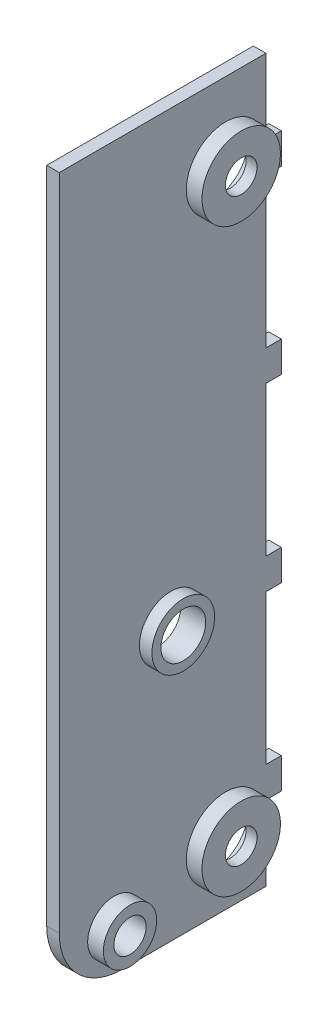
SolidWorks part; units mm, degrees
ref_plane "Front Plane" through (0, 0, 0) normal (0, 0, 1) x (1, 0, 0)
ref_plane "Top Plane" through (0, 0, 0) normal (0, 1, 0) x (1, 0, 0)
ref_plane "Right Plane" through (0, 0, 0) normal (1, 0, 0) x (0, 0, -1)
sketch "Sketch1" plane through (0, 0, 0) normal (0, 0, 1) x (1, 0, 0)
  line L1 (-100, -115) -> (100, -115)
  line L2 (-100, -115) -> (-100, 115)
  line L3 (-100, 115) -> (100, 115)
  line L4 (100, -115) -> (100, 115)
  line L5 (-100, -115) -> (100, 115) construction
  line L6 (-100, 115) -> (100, -115) construction
  point P0 (0, 0)
  dimension "D1" = 230
  dimension "D2" = 200
extrude "Boss-Extrude1" add sketch "Sketch1" along normal blind 70
sketch "Sketch2" plane through (0, 0, 70) normal (0, 0, 1) x (1, 0, 0)
  line L0 (100, 115) -> (-100, 115) construction
  line L1 (-96, -111) -> (96, -111)
  line L2 (-96, -111) -> (-96, 111)
  line L3 (-96, 111) -> (96, 111)
  line L4 (96, -111) -> (96, 111)
  line L5 (-96, -111) -> (96, 111) construction
  line L6 (-96, 111) -> (96, -111) construction
  line L7 (-100, 115) -> (-100, -115) construction
  point P0 (0, 0)
  dimension "D1" = 4
  dimension "D2" = 4
extrude "Cut-Extrude1" cut sketch "Sketch2" against normal blind 66
sketch "Sketch4" plane through (0, -115, 0) normal (0, -1, 0) x (1, 0, 0)
  line L0 (-100, 70) -> (-100, 0) construction
  line L1 (-98, 45) -> (98, 45)
  line L2 (-98, 45) -> (-98, 70)
  line L3 (-98, 70) -> (98, 70)
  line L4 (98, 45) -> (98, 70)
  line L5 (100, 70) -> (100, 0) construction
  line L6 (-100, 70) -> (100, 70) construction
  dimension "D1" = 2
  dimension "D2" = 2
  dimension "D3" = 0
  dimension "D4" = 25
extrude "Cut-Extrude3" cut sketch "Sketch4" against normal blind 10
sketch "Sketch10" plane through (0, 0, 4) normal (0, 0, 1) x (1, 0, 0)
  line L0 (-96, 111) -> (-96, -111) construction
  line L1 (-96, -111) -> (96, -111) construction
  circle A0 centre (0, -11) radius 5
  dimension "D1" = 10
  dimension "D2" = 96
  dimension "D3" = 100
extrude "Cut-Extrude8" cut sketch "Sketch10" against normal through all
sketch "Sketch11" plane through (0, 0, 70) normal (0, 0, 1) x (1, 0, 0)
  line L0 (-98, -105) -> (-98, -115) construction
  line L1 (-98, -105) -> (-100, -105)
  line L2 (-98, -105) -> (-98, -115)
  line L3 (-98, -115) -> (-100, -115)
  line L4 (-100, -105) -> (-100, -115)
  dimension "D1" = 10
extrude "Boss-Extrude2" add sketch "Sketch11" along normal blind 20
sketch "Sketch12" plane through (0, 0, 90) normal (0, 0, 1) x (1, 0, 0)
  line L0 (-100, -105) -> (-100, -115) construction
  line L1 (-100, -107.5) -> (-98, -107.5)
  line L2 (-100, -107.5) -> (-100, -112.5)
  line L3 (-100, -112.5) -> (-98, -112.5)
  line L4 (-98, -107.5) -> (-98, -112.5)
  line L5 (-98, -115) -> (-98, -105) construction
  line L6 (-98, -105) -> (-100, -105) construction
  dimension "D1" = 2.5
  dimension "D2" = 5
extrude "Cut-Extrude9" cut sketch "Sketch12" against normal blind 20
fillet "Fillet1" radius 2.5 2 edges at (-99, -112.5, 70) (-99, -107.5, 70)
sketch "Sketch13" plane through (0, 0, 70) normal (0, 0, 1) x (1, 0, 0)
  line L0 (98, -115) -> (100, -115) construction
  line L1 (98, -105) -> (100, -105)
  line L2 (98, -105) -> (98, -115)
  line L3 (98, -115) -> (100, -115)
  line L4 (100, -105) -> (100, -115)
  dimension "D1" = 0
  dimension "D2" = 2
extrude "Boss-Extrude3" add sketch "Sketch13" along normal blind 20
sketch "Sketch14" plane through (0, 0, 90) normal (0, 0, 1) x (1, 0, 0)
  line L0 (98, -105) -> (98, -115) construction
  line L1 (98, -107.5) -> (100, -107.5)
  line L2 (98, -107.5) -> (98, -112.5)
  line L3 (98, -112.5) -> (100, -112.5)
  line L4 (100, -107.5) -> (100, -112.5)
  line L5 (100, -115) -> (100, -105) construction
  line L6 (98, -105) -> (96, -105) construction
  dimension "D1" = 2.5
  dimension "D2" = 5
extrude "Cut-Extrude10" cut sketch "Sketch14" against normal blind 20
fillet "Fillet2" radius 2.5 2 edges at (99, -112.5, 70) (99, -107.5, 70)
sketch "Sketch15" plane through (0, 115, 0) normal (0, 1, 0) x (1, 0, 0)
  line L0 (100, -70) -> (-100, -70) construction
  line L1 (96, -70) -> (-96, -70)
  line L2 (96, -70) -> (96, -4)
  line L3 (96, -4) -> (-96, -4)
  line L4 (-96, -70) -> (-96, -4)
  line L5 (-100, -70) -> (-100, 0) construction
  line L6 (100, -70) -> (100, 0) construction
  line L7 (100, 0) -> (-100, 0) construction
  dimension "D1" = 4
  dimension "D2" = 4
  dimension "D3" = 4
extrude "Cut-Extrude11" cut sketch "Sketch15" against normal through all
sketch "Sketch16" plane through (-98, 0, 0) normal (1, 0, 0) x (0, 0, -1)
  line L0 (-90, -107.5) -> (-72.5, -107.5)
  line L1 (-72.5, -112.5) -> (-90, -112.5)
  line L2 (-90, -112.5) -> (-90, -115)
  line L3 (-90, -115) -> (-45, -115)
  line L4 (-45, -115) -> (-45, -105)
  line L5 (-45, -105) -> (-90, -105)
  line L6 (-90, -105) -> (-90, -107.5)
  arc A0 (-72.5, -107.5) -> (-72.5, -112.5) centre (-72.5, -110) cw
extrude "Boss-Extrude4" add sketch "Sketch16" along normal blind 2
sketch "Sketch18" plane through (100, 0, 0) normal (1, 0, 0) x (0, 0, -1)
  line L0 (-70, -105) -> (-70, 115) construction
  line L1 (-70, 115) -> (0, 115) construction
  circle A0 centre (-34.45, -28.4) radius 7.15
  dimension "D2" = 14.3
  dimension "D1" = 35.55
  dimension "D3" = 143.4
extrude "Cut-Extrude12" cut sketch "Sketch18" against normal through all
sketch "Sketch19" plane through (100, 0, 0) normal (1, 0, 0) x (0, 0, -1)
  line L0 (-90, -115) -> (0, -115) construction
  line L1 (0, -115) -> (0, 115) construction
  circle A0 centre (-17, -95) radius 5.05
  dimension "D1" = 10.1
  dimension "D2" = 20
  dimension "D3" = 17
extrude "Cut-Extrude13" cut sketch "Sketch19" against normal through all
sketch "Sketch20" plane through (100, 0, 0) normal (1, 0, 0) x (0, 0, -1)
  line L0 (-70, 115) -> (0, 115) construction
  line L1 (0, -115) -> (0, 115) construction
  circle A0 centre (-17, 90) radius 5.05
  dimension "D1" = 10.1
  dimension "D2" = 25
  dimension "D3" = 17
extrude "Cut-Extrude14" cut sketch "Sketch20" against normal through all
sketch "Sketch17" plane through (98, 0, 0) normal (-1, 0, 0) x (0, 0, 1)
  line L0 (90, -107.5) -> (72.5, -107.5)
  line L1 (72.5, -112.5) -> (90, -112.5)
  line L2 (90, -112.5) -> (90, -115)
  line L3 (90, -115) -> (45, -115)
  line L4 (45, -115) -> (45, -105)
  line L5 (45, -105) -> (90, -105)
  line L6 (90, -105) -> (90, -107.5)
  arc A0 (72.5, -107.5) -> (72.5, -112.5) centre (72.5, -110) ccw
extrude "Boss-Extrude5" add sketch "Sketch17" along normal blind 2
sketch "Sketch21" plane through (100, 0, 0) normal (1, 0, 0) x (0, 0, -1)
  line L1 (-90, -115) -> (-70, -115)
  line L2 (-90, -115) -> (-90, -105)
  line L3 (-90, -105) -> (-70, -105)
  line L4 (-70, -115) -> (-70, -105)
extrude "Cut-Extrude15" cut sketch "Sketch21" against normal through all
sketch "Sketch22" plane through (0, 0, 4) normal (0, 0, 1) x (1, 0, 0)
  line L0 (96, 115) -> (-96, 115) construction
  line L1 (46, 75) -> (-46, 75)
  line L2 (46, 75) -> (46, 115)
  line L3 (46, 115) -> (-46, 115)
  line L4 (-46, 75) -> (-46, 115)
  line L5 (96, -115) -> (96, 115) construction
  line L6 (-96, 115) -> (-96, -115) construction
  dimension "D1" = 50
  dimension "D2" = 50
  dimension "D3" = 40
extrude "Cut-Extrude16" cut sketch "Sketch22" against normal blind 10
sketch "Sketch24" plane through (100, 0, 0) normal (1, 0, 0) x (0, 0, -1)
  line L0 (-70, -115) -> (-70, 115) construction
  line L1 (-70, -115) -> (0, -115) construction
  circle A0 centre (-52.45, -102) radius 5.15
  dimension "D1" = 10.3
  dimension "D2" = 17.55
  dimension "D3" = 13
extrude "Cut-Extrude18" cut sketch "Sketch24" against normal through all
fillet "Fillet3" radius 20 1 edges at (98, -115, 70)
fillet "Fillet4" radius 20 1 edges at (-98, -115, 70)
sketch "Sketch25" plane through (0, 115, 0) normal (0, 1, 0) x (1, 0, 0)
  line L0 (-100, -70) -> (-100, 0) construction
  line L1 (100, 0) -> (-100, 0)
  line L2 (100, 0) -> (100, -4.1191)
  line L3 (100, -4.1191) -> (-100, -4.1191)
  line L4 (-100, 0) -> (-100, -4.1191)
extrude "Cut-Extrude19" cut sketch "Sketch25" against normal through all
sketch "Sketch26" plane through (0, 115, 0) normal (0, 1, 0) x (1, 0, 0)
  line L1 (-96, -70) -> (-100, -70)
  line L2 (-96, -70) -> (-96, -4.1191)
  line L3 (-96, -4.1191) -> (-100, -4.1191)
  line L4 (-100, -70) -> (-100, -4.1191)
extrude "Cut-Extrude20" cut sketch "Sketch26" against normal through all
sketch "Sketch27" plane through (0, 0, 4.1191) normal (0, 0, -1) x (-1, 0, 0)
  line L0 (-100, -115) -> (-100, 115) construction
  line L1 (-100, -91.15) -> (-96, -91.15)
  line L2 (-100, -91.15) -> (-100, -81.35)
  line L3 (-100, -81.35) -> (-96, -81.35)
  line L4 (-96, -91.15) -> (-96, -81.35)
  line L5 (-96, 115) -> (-96, -115) construction
  line L6 (-96, -115) -> (-100, -115) construction
  dimension "D1" = 9.8
  dimension "D2" = 23.85
extrude "Boss-Extrude6" add sketch "Sketch27" along normal blind 4.9
sketch "Sketch28" plane through (0, 0, 4.1191) normal (0, 0, -1) x (-1, 0, 0)
  line L0 (-100, -81.35) -> (-100, 115) construction
  line L1 (-100, -23.85) -> (-96, -23.85)
  line L2 (-100, -23.85) -> (-100, -33.65)
  line L3 (-100, -33.65) -> (-96, -33.65)
  line L4 (-96, -23.85) -> (-96, -33.65)
  line L5 (-96, 115) -> (-96, -81.35) construction
  line L6 (-96, -115) -> (-100, -115) construction
  dimension "D2" = 9.8
  dimension "D3" = 81.35
extrude "Boss-Extrude7" add sketch "Sketch28" along normal blind 4.9
ref_plane "Plane1" through (0, 0, 0) normal (0, 1, 0) x (1, 0, 0)
mirror "Mirror1" about plane through (0, 0, 0) normal (0, 1, 0) of "Boss-Extrude7", "Boss-Extrude6"
sketch "Sketch29" plane through (96, 0, 0) normal (-1, 0, 0) x (0, 0, 1)
  circle A0 centre (17, 90) radius 5.05
  circle A1 centre (17, 90) radius 12.5
  dimension "D1" = 25
  dimension "D2" = 10.1
extrude "Boss-Extrude8" add sketch "Sketch29" against normal blind 9
sketch "Sketch30" plane through (100, 0, 0) normal (1, 0, 0) x (0, 0, -1)
  circle A0 centre (-52.45, -102) radius 5.15
  circle A1 centre (-52.45, -102) radius 8.5
  dimension "D1" = 10.3
  dimension "D2" = 17
extrude "Boss-Extrude9" add sketch "Sketch30" along normal blind 5
sketch "Sketch32" plane through (100, 0, 0) normal (1, 0, 0) x (0, 0, -1)
  circle A0 centre (-34.45, -28.4) radius 7.15
  circle A1 centre (-34.45, -28.4) radius 10
  dimension "D1" = 14.3
  dimension "D2" = 20
extrude "Boss-Extrude10" add sketch "Sketch32" along normal blind 4
sketch "Sketch33" plane through (96, 0, 0) normal (-1, 0, 0) x (0, 0, 1)
  circle A0 centre (17, 90) radius 11.2
  dimension "D1" = 22.4
extrude "Cut-Extrude21" cut sketch "Sketch33" against normal blind 5.5
ref_plane "Plane2" through (0, -2.5, 0) normal (0, 1, 0) x (1, 0, 0)
mirror "Mirror2" about plane through (0, -2.5, 0) normal (0, 1, 0) of "Boss-Extrude8", "Cut-Extrude21"
